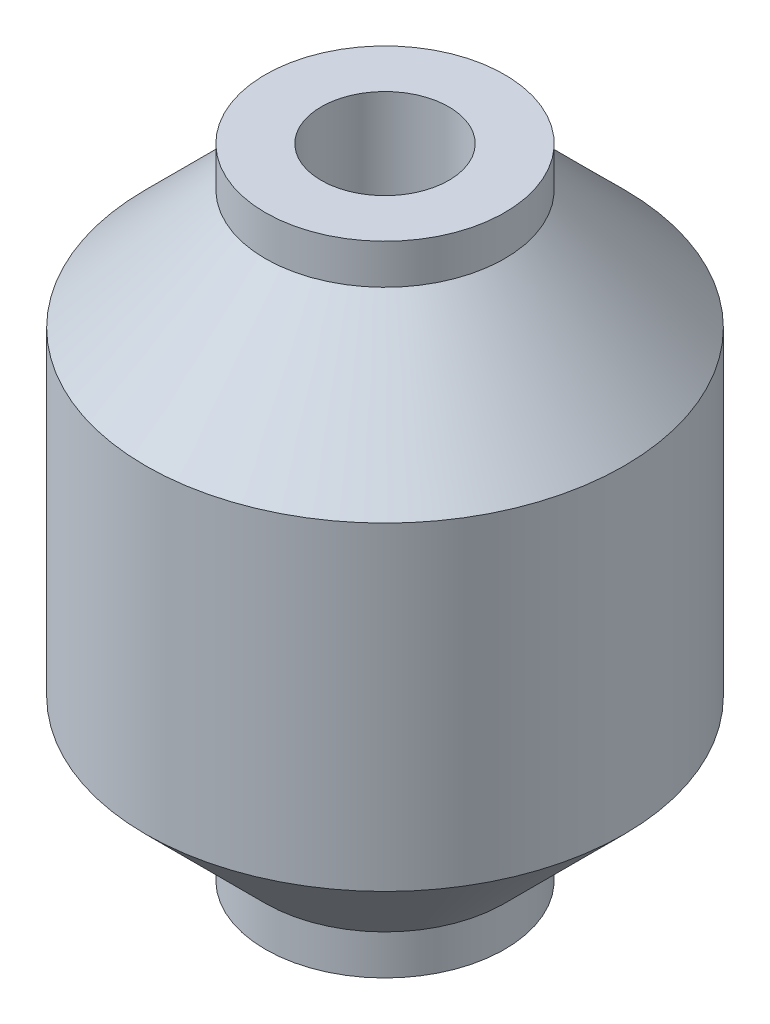
SolidWorks part; units mm, degrees
ref_plane "Front Plane" through (0, 0, 0) normal (0, 0, 1) x (1, 0, 0)
ref_plane "Top Plane" through (0, 0, 0) normal (0, 1, 0) x (1, 0, 0)
ref_plane "Right Plane" through (0, 0, 0) normal (1, 0, 0) x (0, 0, -1)
sketch "Sketch1" plane through (0, 0, 0) normal (0, 1, 0) x (1, 0, 0)
  circle A1 centre (0, 0) radius 6
  dimension "D1" = 12
extrude "Boss-Extrude1" add sketch "Sketch1" along normal mid plane 8
sketch "Sketch2" plane through (0, 4, 0) normal (0, 1, 0) x (1, 0, 0)
  circle A1 centre (0, 0) radius 3
  dimension "D1" = 6
extrude "Boss-Extrude2" add sketch "Sketch2" along normal blind 4
mirror "Mirror1" about plane through (0, 0, 0) normal (0, 1, 0) of "Boss-Extrude2"
sketch "Sketch3" plane through (0, 8, 0) normal (0, 1, 0) x (1, 0, 0)
  circle A0 centre (0, 0) radius 1.6
  dimension "D1" = 3.2
extrude "Cut-Extrude1" cut sketch "Sketch3" against normal up to surface (16 mm away) up to face at (0, -8, 3)
chamfer "Chamfer1" distance 3 angle 45 2 edges at (0, -4, 3) (0, 4, 3)
